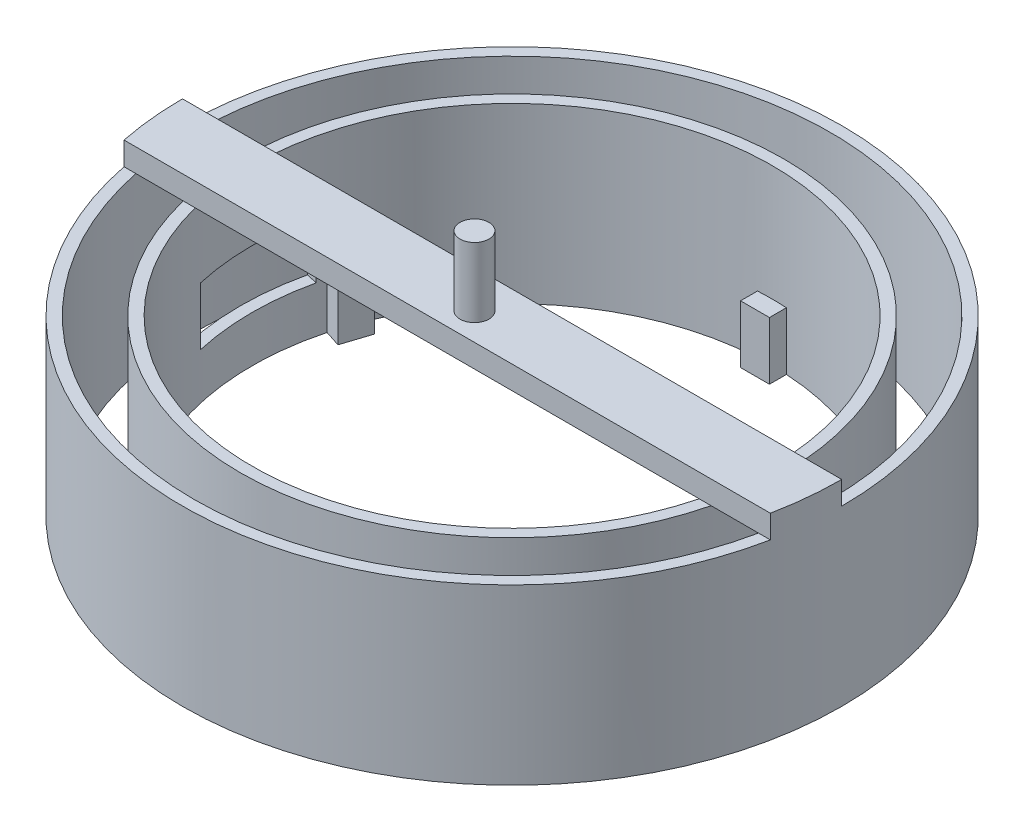
SolidWorks part; units mm, degrees
ref_plane "Front Plane" through (0, 0, 0) normal (0, 0, 1) x (1, 0, 0)
ref_plane "Top Plane" through (0, 0, 0) normal (0, 1, 0) x (1, 0, 0)
ref_plane "Right Plane" through (0, 0, 0) normal (1, 0, 0) x (0, 0, -1)
sketch "Sketch1" plane through (0, 0, 0) normal (0, 1, 0) x (1, 0, 0)
  circle A0 centre (0, 0) radius 22.5
  circle A1 centre (0, 0) radius 23.5
  circle A2 centre (0, 0) radius 27.5
  circle A3 centre (0, 0) radius 28.5
  dimension "D1" = 45
  dimension "D3" = 4
  dimension "D4" = 1
  dimension "D2" = 1
extrude "Boss-Extrude1" add sketch "Sketch1" along normal blind 15 contours A3 A2 | A1 A0 region at (-22.8353, 0, 0) region at (-27.6939, 0, 0)
ref_plane "Plane1" through (0, 15, 0) normal (0, 1, 0) x (1, 0, 0)
ref_plane "Plane2" through (0, 15, 0) normal (0, 1, 0) x (1, 0, 0)
sketch "Sketch3" plane through (0, 15, 0) normal (0, 1, 0) x (1, 0, 0)
  line L0 (-28.5, 0) -> (28.5, 0)
  arc A0 (-28.5, 0) -> (28.5, 0) centre (0, 0) ccw
  dimension "D1" = 57
ref_plane "Plane3" through (0, 4, 0) normal (0, -1, 0) x (-1, 0, 0)
sketch "Sketch4" plane through (0, 4, 0) normal (0, -1, 0) x (-1, 0, 0)
  line L0 (22.9124, 5.2222) -> (21.9374, 5)
  line L1 (22.9124, -5.2222) -> (21.9374, -5)
  line L2 (0, 8.25) -> (0, -8.25) construction
  line L3 (-22.9124, -5.2222) -> (-21.9374, -5)
  line L4 (-22.9124, 5.2222) -> (-21.9374, 5)
  line L5 (-5.2222, -22.9124) -> (-5, -21.9374)
  line L6 (5.2222, -22.9124) -> (5, -21.9374)
  line L7 (-22.9124, 5.2222) -> (-21.9374, 5)
  line L8 (-22.9124, -5.2222) -> (-21.9374, -5)
  arc A0 (21.9374, 5) -> (21.9374, -5) centre (0, 0) cw
  circle A1 centre (0, 0) radius 22.5 construction
  arc A2 (22.9124, 5.2222) -> (22.9124, -5.2222) centre (0, 0) cw
  arc A3 (-22.9124, 5.2222) -> (-22.9124, -5.2222) centre (0, 0) ccw
  arc A4 (-21.9374, 5) -> (-21.9374, -5) centre (0, 0) ccw
  arc A5 (5.2222, -22.9124) -> (-5.2222, -22.9124) centre (0, 0) cw
  arc A6 (5, -21.9374) -> (-5, -21.9374) centre (0, 0) cw
  arc A7 (-22.9124, -5.2222) -> (-22.9124, 5.2222) centre (0, 0) cw
  arc A8 (-21.9374, -5) -> (-21.9374, 5) centre (0, 0) cw
  point P3 (22.5, 0)
  point P30 (0, 0)
  dimension "D1" = 10
  dimension "D2" = 1
extrude "Cut-Extrude2" cut sketch "Sketch4" against normal blind 5 contours A2 L1 A0 L0 | A5 L5 A6 L6 | A4 L3 A3 L4
extrude "Boss-Extrude3" add sketch "Sketch3" along normal blind 2
sketch "Sketch5" plane through (0, 17, 0) normal (0, 1, 0) x (1, 0, 0)
  circle A0 centre (0, -3.2532) radius 1.25
  dimension "D1" = 2.5
  dimension "D2" = 3.2532
extrude "Boss-Extrude4" add sketch "Sketch5" along normal blind 6
sketch "Sketch6" plane through (0, 17, 0) normal (0, 1, 0) x (1, 0, 0)
  line L0 (-27.9418, -5.613) -> (27.9418, -5.613)
  arc A0 (-27.9418, -5.613) -> (27.9418, -5.613) centre (0, 0) ccw
  arc A1 (-28.5, 0) -> (28.5, 0) centre (0, 0) ccw construction
extrude "Cut-Extrude3" cut sketch "Sketch6" against normal blind 2
sketch "Sketch7" plane through (0, 0, 0) normal (0, -1, 0) x (1, 0, 0)
  line L0 (-1.25, -22.5) -> (1.25, -22.5)
  line L2 (-1.25, -22.5) -> (-1.25, -21)
  line L3 (-1.25, -21) -> (1.25, -21)
  line L4 (1.25, -22.5) -> (1.25, -21)
  line L5 (0, -22.5) -> (1.25, -21) construction
  line L6 (-1.25, -21) -> (0, -22.5) construction
  circle A0 centre (0, 0) radius 22.5 construction
  point P0 (0, -22.5)
  dimension "D1" = 1.5
extrude "Boss-Extrude5" add sketch "Sketch7" against normal blind 5
pattern_circular "CirPattern1" count 5 over 360 about axis through (0, 0, 0) along (0, 1, 0) of "Boss-Extrude5"
